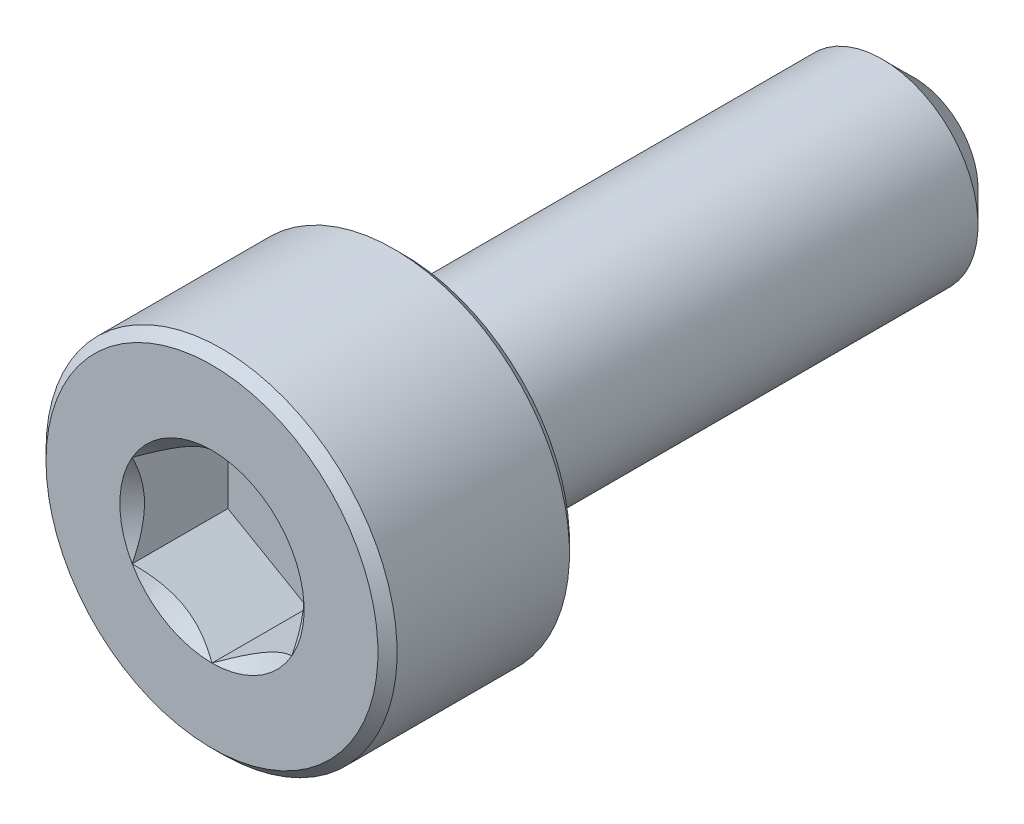
SolidWorks part; units mm, degrees
ref_plane "Front Plane" through (0, 0, 0) normal (0, 0, 1) x (1, 0, 0)
ref_plane "Top Plane" through (0, 0, 0) normal (0, 1, 0) x (1, 0, 0)
ref_plane "Right Plane" through (0, 0, 0) normal (1, 0, 0) x (0, 0, -1)
sketch "Sketch1" plane through (0, 0, 0) normal (1, 0, 0) x (0, 0, -1)
  line L0 (-5.5, 0) -> (5.5, 0) construction
  line L1 (5.5, 0) -> (5.5, 1) construction
  line L2 (5.5, 1) -> (5, 1.5) construction
  line L3 (5, 1.5) -> (-2.5, 1.5) construction
  line L5 (-2.5, 1.5) -> (-2.5, 2.75) construction
  line L6 (-2.5, 2.75) -> (-5.5, 2.75) construction
  line L7 (-5.5, 2.75) -> (-5.5, 0) construction
  line L8 (5.5, 1) -> (5.5, 1.5) construction
  line L9 (5.4688, 1.5541) -> (5.7188, 1.1211) construction
  line L10 (5.7188, 1.1211) -> (5.9688, 1.5541) construction
  line L11 (5.9688, 1.5541) -> (5.4688, 1.5541) construction
  line L12 (5.7188, 1.5541) -> (5.7188, 1.5) construction
  line L13 (5.7188, 1.1211) -> (5.7188, 1.1752) construction
  line L14 (5.6875, 1.1752) -> (5.75, 1.1752) construction
  line L15 (5.5, 1.5) -> (5.9375, 1.5) construction
  line L16 (5.4844, 1.5271) -> (5.9531, 1.5271) construction
  line L17 (5.5, 0) -> (5.5, -1.5) construction
  line L18 (-2.65, 2.75) -> (-2.5, 2.6) construction
  line L19 (-5.35, 2.75) -> (-5.5, 2.6) construction
  point P0 (-5.5, 1.25)
  point P3 (3.75, 1.5)
  point P4 (0, 0)
  point P22 (5.7188, 1.1752)
  point P24 (-2.5, 1.5)
  point P25 (5.7188, 1.5)
  point P28 (5.7188, 1.5271)
  point P29 (3.75, -1.5)
  point P31 (-4, 2.75)
  point P37 (-3.025, 2.75)
  point P38 (-5.275, 2.75)
  point P41 (-4, 0)
  dimension "head height" = 3
  dimension "D1" = 45
  dimension "Head Diameter" = 5.5
  dimension "Thread Size" = 3
  dimension "drive size" = 2.5
  dimension "Thread Pitch" = 0.5
  dimension "D2" = 0.0625
  dimension "D3" = 0.5
  dimension "D4" = 1.75
  dimension "D7" = 0.15
  dimension "D8" = 0.15
  dimension "D9" = 0.15
  dimension "D10" = 0.075
  dimension "D11" = 0.375
  dimension "length" = 8
  dimension "Drive Depth" = 1.5
sketch "Sketch2" plane through (0, 0, 0) normal (1, 0, 0) x (0, 0, -1)
  line L1 (-5.35, 2.75) -> (-2.65, 2.75)
  line L4 (5, 1.5) -> (5.5, 1)
  line L5 (5.5, 1) -> (5.5, 0)
  line L6 (-2.65, 2.75) -> (-2.5, 2.6) construction
  line L7 (5.5, 0) -> (-5.5, 0)
  line L8 (-5.35, 2.75) -> (-5.5, 2.6) construction
  line L9 (-2.65, 2.75) -> (-2.5, 2.6)
  line L10 (-5.35, 2.75) -> (-5.5, 2.6)
  line L11 (-5.5, 2.6) -> (-5.5, 0)
  line L12 (-2.5, 2.6) -> (-2.5, 1.5)
  line L13 (-2.5, 1.5) -> (5, 1.5)
revolve "Revolve1" add sketch "Sketch2" angle 360 about L7
sketch "Sketch3" plane through (0, 0, 5.5) normal (0, 0, 1) x (1, 0, 0)
  line L1 (0, 1.4434) -> (-1.25, 0.7217)
  line L2 (-1.25, 0.7217) -> (-1.25, -0.7217)
  line L3 (-1.25, -0.7217) -> (0, -1.4434)
  line L4 (0, -1.4434) -> (1.25, -0.7217)
  line L5 (1.25, -0.7217) -> (1.25, 0.7217)
  line L6 (1.25, 0.7217) -> (0, 1.4434)
  circle A0 centre (0, 0) radius 1.25 construction
  dimension "D1" = 2.5
extrude "Cut-Extrude1" cut sketch "Sketch3" against normal up to vertex (1.5 mm away) up to point (0, 0, 4)
sketch "Sketch4" plane through (0, 0, 5.5) normal (0, 0, 1) x (1, 0, 0)
  circle A0 centre (0, 0) radius 1.4434
extrude "Cut-Extrude2" cut sketch "Sketch4" against normal blind 0.5 draft 45
ref_plane "Plane1" [suppressed] through (0, 0, 2.5) normal (0, 0, 1) x (1, 0, 0)
split "Split1" [suppressed] bodies to split 106
sketch "Sketch6" [suppressed] plane through (0, 0, -5.5) normal (0, 0, -1) x (-1, 0, 0)
  circle A0 centre (0, 0) radius 1.5
curve "Helix/Spiral1" [suppressed] pitch 0.5 height 8.5 turns 17
sketch "Sketch7" [suppressed] plane through (0, 0, 0) normal (1, 0, 0) x (0, 0, -1)
  line L0 (5.4844, 1.5271) -> (5.9531, 1.5271)
  line L1 (5.9531, 1.5271) -> (5.75, 1.1752)
  line L2 (5.75, 1.1752) -> (5.6875, 1.1752)
  line L3 (5.6875, 1.1752) -> (5.4844, 1.5271)
sweep "Cut-Sweep1" [suppressed] cut profiles "Sketch7" path "Helix/Spiral1"
sketch "Sketch8" [suppressed] plane through (0, 0, 2.5) normal (0, 0, -1) x (-1, 0, 0)
  circle A0 centre (0, 0) radius 1.5
extrude "Boss-Extrude1" [suppressed] add sketch "Sketch8" along normal through all draft 45
ref_plane "Plane2" through (0, 0, 4) normal (0, 0, 1) x (1, 0, 0)
sketch "Sketch9" plane through (0, 0, 4) normal (0, 0, 1) x (1, 0, 0)
  line L0 (0, 2.6744) -> (0.072, 2.7491)
  line L1 (0, 2.6744) -> (-0.072, 2.7491)
  line L2 (0, 2.75) -> (0, 0) construction
  line L3 (-0.072, 2.7491) -> (0, 0) construction
  line L4 (0, 0) -> (0.072, 2.7491) construction
  arc A0 (0.072, 2.7491) -> (-0.072, 2.7491) centre (0, 0) ccw
  circle A1 centre (0, 0) radius 2.6744 construction
  dimension "D1" = 5.5
  dimension "D2" = 5.3487
  dimension "D3" = 3
extrude "Cut-Extrude4" [suppressed] cut sketch "Sketch9" against normal up to vertex and the other way up to vertex
pattern_circular "CirPattern2" [suppressed] count 96 over 360 about axis through (0, 0, 5.5) along (0, 0, -1) of bodies 113
equation "\"D2@Sketch1\" = \"Thread Pitch@Sketch1\" / 8"
equation "\"D3@Sketch1\" = \"Thread Pitch@Sketch1\""
equation "\"D3@Helix/Spiral1\" = \"length@Sketch1\" + \"Thread Pitch@Sketch1\""
equation "\"D4@Helix/Spiral1\" = \"Thread Pitch@Sketch1\""
equation "\"D4@Sketch1\" = \"Thread Pitch@Sketch1\" * 3.5"
equation "\"D7@Sketch1\"=\"head height@Sketch1\"*.05"
equation "\"D8@Sketch1\"=\"D7@Sketch1\""
equation "\"D9@Sketch1\"=\"D7@Sketch1\""
equation "\"D10@Sketch1\"=\"D7@Sketch1\"/2"
equation "\"D11@Sketch1\"=\"D10@Sketch1\"*5"
equation "\"D1@CirPattern2\"=( 360 / \"D3@Sketch9\" )*0.8"
equation "\"D1@Sketch3\" = \"drive size@Sketch1\""
equation "\"D2@Sketch9\"=\"Head Diameter@Sketch1\" * 0.9725"
